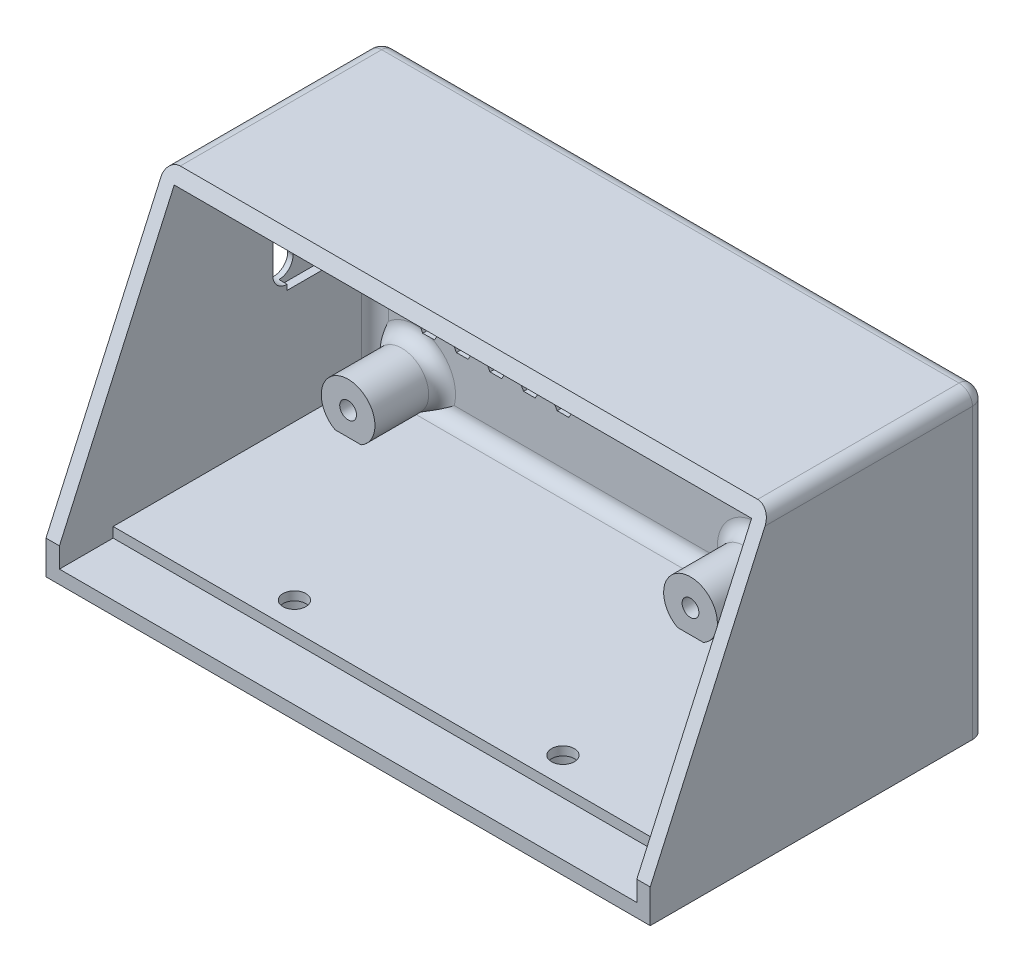
SolidWorks part; units mm, degrees
ref_plane "前视基准面" through (0, 0, 0) normal (0, 0, 1) x (1, 0, 0)
ref_plane "上视基准面" through (0, 0, 0) normal (0, 1, 0) x (1, 0, 0)
ref_plane "右视基准面" through (0, 0, 0) normal (1, 0, 0) x (0, 0, -1)
sketch "草图1" plane through (0, 0, 0) normal (0, 0, 1) x (1, 0, 0)
  line L1 (0, 0) -> (90, 0)
  line L2 (0, 0) -> (0, 45)
  line L3 (0, 45) -> (90, 45)
  line L4 (90, 0) -> (90, 45)
  dimension "D1" = 90
  dimension "D2" = 45
extrude "凸台-拉伸1" add sketch "草图1" along normal blind 50
sketch "草图2" plane through (90, 0, 0) normal (1, 0, 0) x (0, 0, -1)
  line L0 (-32, 45) -> (-50, 5)
  line L1 (-50, 45) -> (0, 45) construction
  line L2 (-50, 0) -> (-50, 45) construction
  line L3 (-50, 5) -> (-50, 45)
  line L4 (-50, 45) -> (-32, 45)
  dimension "D1" = 18
  dimension "D2" = 40
extrude "切除-拉伸1" cut sketch "草图2" against normal through all
ref_plane "基准面1" through (0, 0, 70) normal (0, 0, 1) x (1, 0, 0)
sketch "草图3" plane through (0, 0, 70) normal (0, 0, 1) x (1, 0, 0)
  line L0 (0, 5) -> (0, 45) construction
  line L1 (2, 2) -> (88, 2)
  line L2 (2, 2) -> (2, 43)
  line L3 (2, 43) -> (88, 43)
  line L4 (88, 2) -> (88, 43)
  line L5 (0, 45) -> (90, 45) construction
  line L6 (0, 0) -> (90, 0) construction
  line L7 (90, 5) -> (90, 45) construction
  dimension "D1" = 2
  dimension "D2" = 2
  dimension "D3" = 2
  dimension "D4" = 2
extrude "切除-拉伸2" cut sketch "草图3" against normal offset from surface (67 mm away) 3 up to face at (45, 22.5, 0)
sketch "草图4" plane through (0, 0, 3) normal (0, 0, 1) x (1, 0, 0)
  line L0 (2, 2) -> (88, 2) construction
  line L1 (2, 5) -> (2, 43) construction
  circle A0 centre (8, 38) radius 4
  circle A1 centre (59, 38) radius 4
  circle A2 centre (8, 7) radius 4
  circle A3 centre (59, 7) radius 4
  dimension "D1" = 8
  dimension "D2" = 8
  dimension "D3" = 8
  dimension "D4" = 8
  dimension "D5" = 51
  dimension "D6" = 31
  dimension "D7" = 5
  dimension "D8" = 6
extrude "凸台-拉伸2" add sketch "草图4" along normal blind 10
sketch "草图5" plane through (0, 0, 13) normal (0, 0, 1) x (1, 0, 0)
  circle A0 centre (8, 38) radius 1.25
  circle A1 centre (59, 38) radius 1.25
  circle A2 centre (8, 7) radius 1.25
  circle A3 centre (59, 7) radius 1.25
  dimension "D1" = 2.5
  dimension "D2" = 2.5
  dimension "D3" = 2.5
  dimension "D4" = 2.5
extrude "切除-拉伸3" cut sketch "草图5" against normal blind 7
ref_plane "基准面2" through (0, 0, 9) normal (0, 0, 1) x (1, 0, 0)
sketch "草图6" plane through (0, 0, 9) normal (0, 0, 1) x (1, 0, 0)
  circle A0 centre (8, 38) radius 2.5
  circle A1 centre (59, 38) radius 2.5
  circle A2 centre (8, 7) radius 2.5
  circle A3 centre (59, 7) radius 2.5
  dimension "D1" = 5
  dimension "D2" = 5
  dimension "D3" = 5
  dimension "D4" = 5
extrude "切除-拉伸4" cut sketch "草图6" against normal blind 3
sketch "草图7" plane through (0, 0, 0) normal (-1, 0, 0) x (0, 0, 1)
  line L0 (16.1, 30.1) -> (16.1, 23.9) construction
  line L1 (18.2, 30.1) -> (18.2, 23.9)
  line L2 (14, 30.1) -> (14, 23.9)
  line L3 (0, 45) -> (0, 0) construction
  line L4 (32, 45) -> (0, 45) construction
  arc A0 (18.2, 30.1) -> (14, 30.1) centre (16.1, 30.1) ccw
  arc A1 (14, 23.9) -> (18.2, 23.9) centre (16.1, 23.9) ccw
  point P2 (16.1, 27)
  dimension "D1" = 6.2
  dimension "D2" = 4.2
  dimension "D3" = 16.1
  dimension "D4" = 18
extrude "切除-拉伸5" cut sketch "草图7" against normal up to surface (2 mm away) up to face at (2, 19, 27.78)
sketch "草图8" plane through (2, 0, 0) normal (1, 0, 0) x (0, 0, -1)
  line L0 (-3, 43) -> (-3, 2) construction
  line L1 (-16.1, 33) -> (-3, 33)
  line L2 (-16.1, 33) -> (-16.1, 21)
  line L3 (-16.1, 21) -> (-3, 21)
  line L4 (-3, 33) -> (-3, 21)
  line L5 (-14, 23.9) -> (-14, 30.1) construction
  arc A0 (-14, 30.1) -> (-18.2, 30.1) centre (-16.1, 30.1) ccw construction
  point P9 (-16.1, 32.2)
  point P12 (-14, 27)
  point P13 (-16.1, 27)
  dimension "D1" = 12
extrude "切除-拉伸6" cut sketch "草图8" against normal blind 1.2
sketch "草图9" plane through (0, 0, 0) normal (0, 0, -1) x (-1, 0, 0)
  line L0 (-90, 45) -> (0, 45) construction
  line L1 (-8.2679, 29) -> (-9.134, 30.5)
  line L2 (-9.134, 30.5) -> (-10.866, 30.5)
  line L3 (-10.866, 30.5) -> (-11.7321, 29)
  line L4 (-11.7321, 29) -> (-10.866, 27.5)
  line L5 (-10.866, 27.5) -> (-9.134, 27.5)
  line L6 (-9.134, 27.5) -> (-8.2679, 29)
  line L9 (-14.134, 30.5) -> (-15.866, 30.5)
  line L10 (-13.2679, 29) -> (-14.134, 30.5)
  line L11 (-14.134, 27.5) -> (-13.2679, 29)
  line L12 (-15.866, 27.5) -> (-14.134, 27.5)
  line L13 (-16.7321, 29) -> (-15.866, 27.5)
  line L14 (-15.866, 30.5) -> (-16.7321, 29)
  line L15 (-19.134, 30.5) -> (-20.866, 30.5)
  line L16 (-18.2679, 29) -> (-19.134, 30.5)
  line L17 (-19.134, 27.5) -> (-18.2679, 29)
  line L18 (-20.866, 27.5) -> (-19.134, 27.5)
  line L19 (-21.7321, 29) -> (-20.866, 27.5)
  line L20 (-20.866, 30.5) -> (-21.7321, 29)
  line L21 (-24.134, 30.5) -> (-25.866, 30.5)
  line L22 (-23.2679, 29) -> (-24.134, 30.5)
  line L23 (-24.134, 27.5) -> (-23.2679, 29)
  line L24 (-25.866, 27.5) -> (-24.134, 27.5)
  line L25 (-26.7321, 29) -> (-25.866, 27.5)
  line L26 (-25.866, 30.5) -> (-26.7321, 29)
  line L27 (-29.134, 30.5) -> (-30.866, 30.5)
  line L28 (-28.2679, 29) -> (-29.134, 30.5)
  line L29 (-29.134, 27.5) -> (-28.2679, 29)
  line L30 (-30.866, 27.5) -> (-29.134, 27.5)
  line L31 (-31.7321, 29) -> (-30.866, 27.5)
  line L32 (-30.866, 30.5) -> (-31.7321, 29)
  line L39 (0, 45) -> (0, 0) construction
  line L40 (-8.2679, 24) -> (-9.134, 25.5)
  line L41 (-9.134, 25.5) -> (-10.866, 25.5)
  line L42 (-10.866, 25.5) -> (-11.7321, 24)
  line L43 (-11.7321, 24) -> (-10.866, 22.5)
  line L44 (-10.866, 22.5) -> (-9.134, 22.5)
  line L45 (-9.134, 22.5) -> (-8.2679, 24)
  line L46 (-14.134, 25.5) -> (-15.866, 25.5)
  line L47 (-13.2679, 24) -> (-14.134, 25.5)
  line L48 (-14.134, 22.5) -> (-13.2679, 24)
  line L49 (-15.866, 22.5) -> (-14.134, 22.5)
  line L50 (-16.7321, 24) -> (-15.866, 22.5)
  line L51 (-15.866, 25.5) -> (-16.7321, 24)
  line L52 (-19.134, 25.5) -> (-20.866, 25.5)
  line L53 (-18.2679, 24) -> (-19.134, 25.5)
  line L54 (-19.134, 22.5) -> (-18.2679, 24)
  line L55 (-20.866, 22.5) -> (-19.134, 22.5)
  line L56 (-21.7321, 24) -> (-20.866, 22.5)
  line L57 (-20.866, 25.5) -> (-21.7321, 24)
  line L58 (-24.134, 25.5) -> (-25.866, 25.5)
  line L59 (-23.2679, 24) -> (-24.134, 25.5)
  line L60 (-24.134, 22.5) -> (-23.2679, 24)
  line L61 (-25.866, 22.5) -> (-24.134, 22.5)
  line L62 (-26.7321, 24) -> (-25.866, 22.5)
  line L63 (-25.866, 25.5) -> (-26.7321, 24)
  line L64 (-29.134, 25.5) -> (-30.866, 25.5)
  line L65 (-28.2679, 24) -> (-29.134, 25.5)
  line L66 (-29.134, 22.5) -> (-28.2679, 24)
  line L67 (-30.866, 22.5) -> (-29.134, 22.5)
  line L68 (-31.7321, 24) -> (-30.866, 22.5)
  line L69 (-30.866, 25.5) -> (-31.7321, 24)
  line L70 (-8.2679, 19) -> (-9.134, 20.5)
  line L71 (-9.134, 20.5) -> (-10.866, 20.5)
  line L72 (-10.866, 20.5) -> (-11.7321, 19)
  line L73 (-11.7321, 19) -> (-10.866, 17.5)
  line L74 (-10.866, 17.5) -> (-9.134, 17.5)
  line L75 (-9.134, 17.5) -> (-8.2679, 19)
  line L76 (-14.134, 20.5) -> (-15.866, 20.5)
  line L77 (-13.2679, 19) -> (-14.134, 20.5)
  line L78 (-14.134, 17.5) -> (-13.2679, 19)
  line L79 (-15.866, 17.5) -> (-14.134, 17.5)
  line L80 (-16.7321, 19) -> (-15.866, 17.5)
  line L81 (-15.866, 20.5) -> (-16.7321, 19)
  line L82 (-19.134, 20.5) -> (-20.866, 20.5)
  line L83 (-18.2679, 19) -> (-19.134, 20.5)
  line L84 (-19.134, 17.5) -> (-18.2679, 19)
  line L85 (-20.866, 17.5) -> (-19.134, 17.5)
  line L86 (-21.7321, 19) -> (-20.866, 17.5)
  line L87 (-20.866, 20.5) -> (-21.7321, 19)
  line L88 (-24.134, 20.5) -> (-25.866, 20.5)
  line L89 (-23.2679, 19) -> (-24.134, 20.5)
  line L90 (-24.134, 17.5) -> (-23.2679, 19)
  line L91 (-25.866, 17.5) -> (-24.134, 17.5)
  line L92 (-26.7321, 19) -> (-25.866, 17.5)
  line L93 (-25.866, 20.5) -> (-26.7321, 19)
  line L94 (-29.134, 20.5) -> (-30.866, 20.5)
  line L95 (-28.2679, 19) -> (-29.134, 20.5)
  line L96 (-29.134, 17.5) -> (-28.2679, 19)
  line L97 (-30.866, 17.5) -> (-29.134, 17.5)
  line L98 (-31.7321, 19) -> (-30.866, 17.5)
  line L99 (-30.866, 20.5) -> (-31.7321, 19)
  line L100 (-8.2679, 14) -> (-9.134, 15.5)
  line L101 (-9.134, 15.5) -> (-10.866, 15.5)
  line L102 (-10.866, 15.5) -> (-11.7321, 14)
  line L103 (-11.7321, 14) -> (-10.866, 12.5)
  line L104 (-10.866, 12.5) -> (-9.134, 12.5)
  line L105 (-9.134, 12.5) -> (-8.2679, 14)
  line L106 (-14.134, 15.5) -> (-15.866, 15.5)
  line L107 (-13.2679, 14) -> (-14.134, 15.5)
  line L108 (-14.134, 12.5) -> (-13.2679, 14)
  line L109 (-15.866, 12.5) -> (-14.134, 12.5)
  line L110 (-16.7321, 14) -> (-15.866, 12.5)
  line L111 (-15.866, 15.5) -> (-16.7321, 14)
  line L112 (-19.134, 15.5) -> (-20.866, 15.5)
  line L113 (-18.2679, 14) -> (-19.134, 15.5)
  line L114 (-19.134, 12.5) -> (-18.2679, 14)
  line L115 (-20.866, 12.5) -> (-19.134, 12.5)
  line L116 (-21.7321, 14) -> (-20.866, 12.5)
  line L117 (-20.866, 15.5) -> (-21.7321, 14)
  line L118 (-24.134, 15.5) -> (-25.866, 15.5)
  line L119 (-23.2679, 14) -> (-24.134, 15.5)
  line L120 (-24.134, 12.5) -> (-23.2679, 14)
  line L121 (-25.866, 12.5) -> (-24.134, 12.5)
  line L122 (-26.7321, 14) -> (-25.866, 12.5)
  line L123 (-25.866, 15.5) -> (-26.7321, 14)
  line L124 (-29.134, 15.5) -> (-30.866, 15.5)
  line L125 (-28.2679, 14) -> (-29.134, 15.5)
  line L126 (-29.134, 12.5) -> (-28.2679, 14)
  line L127 (-30.866, 12.5) -> (-29.134, 12.5)
  line L128 (-31.7321, 14) -> (-30.866, 12.5)
  line L129 (-30.866, 15.5) -> (-31.7321, 14)
  circle A0 centre (-10, 29) radius 1.5 construction
  circle A1 centre (-15, 29) radius 1.5 construction
  circle A2 centre (-20, 29) radius 1.5 construction
  circle A3 centre (-25, 29) radius 1.5 construction
  circle A4 centre (-30, 29) radius 1.5 construction
  circle A5 centre (-10, 24) radius 1.5 construction
  circle A6 centre (-15, 24) radius 1.5 construction
  circle A7 centre (-20, 24) radius 1.5 construction
  circle A8 centre (-25, 24) radius 1.5 construction
  circle A9 centre (-30, 24) radius 1.5 construction
  circle A10 centre (-10, 19) radius 1.5 construction
  circle A11 centre (-15, 19) radius 1.5 construction
  circle A12 centre (-20, 19) radius 1.5 construction
  circle A13 centre (-25, 19) radius 1.5 construction
  circle A14 centre (-30, 19) radius 1.5 construction
  circle A15 centre (-10, 14) radius 1.5 construction
  circle A16 centre (-15, 14) radius 1.5 construction
  circle A17 centre (-20, 14) radius 1.5 construction
  circle A18 centre (-25, 14) radius 1.5 construction
  circle A19 centre (-30, 14) radius 1.5 construction
  dimension "D1" = 3
  dimension "D2" = 16
  dimension "D3" = 10
  dimension "D4" = 5
  dimension "D5" = 4
extrude "切除-拉伸7" cut sketch "草图9" against normal up to surface (3 mm away) up to face at (55, 7, 3)
sketch "草图10" plane through (0, 0, 3) normal (0, 0, 1) x (1, 0, 0)
  line L0 (20.866, 30.5) -> (19.134, 30.5) construction
  line L1 (88, 43) -> (2, 43) construction
  circle A0 centre (20, 36.8) radius 4.5
  circle A1 centre (20, 36.8) radius 3.5
  point P6 (20, 30.5)
  dimension "D1" = 9
  dimension "D2" = 7
  dimension "D3" = 6.2
extrude "凸台-拉伸3" add sketch "草图10" along normal blind 3
sketch "草图11" plane through (0, 0, 3) normal (0, 0, 1) x (1, 0, 0)
  circle A0 centre (20, 36.8) radius 2
  dimension "D1" = 4
extrude "切除-拉伸8" cut sketch "草图11" against normal through all
sketch "草图13" plane through (0, 2, 0) normal (0, 1, 0) x (1, 0, 0)
  line L0 (88, -3) -> (88, -50) construction
  line L1 (2, -3) -> (88, -3)
  line L2 (2, -3) -> (2, -42)
  line L3 (2, -42) -> (88, -42)
  line L4 (88, -3) -> (88, -42)
  line L5 (88, -50) -> (2, -50) construction
  dimension "D1" = 8
extrude "凸台-拉伸5" add sketch "草图13" along normal blind 1.5
sketch "草图12" plane through (0, 0, 0) normal (0, -1, 0) x (1, 0, 0)
  line L0 (45, 50) -> (45, -10.3613) construction
  line L1 (0, 50) -> (90, 50) construction
  circle A0 centre (25, 38) radius 1.7
  circle A1 centre (65, 38) radius 1.7
  dimension "D1" = 3.4
  dimension "D3" = 12
  dimension "D2" = 20
extrude "切除-拉伸9" cut sketch "草图12" against normal up to next
sketch "草图14" plane through (0, 0, 0) normal (0, -1, 0) x (1, 0, 0)
  circle A0 centre (25, 38) radius 3.1
  circle A1 centre (65, 38) radius 3.1
  dimension "D1" = 6.2
  dimension "D2" = 6.2
extrude "切除-拉伸10" cut sketch "草图14" against normal blind 2.2
fillet "圆角2" radius 2 5 edges at (0, 22.5, 0) (90, 22.5, 0) (45, 45, 0) (90, 45, 16) (0, 45, 16)
fillet "圆角3" radius 2 11 edges at (2, 38, 3) (2, 12.25, 3) (33.5, 3.5, 3) (74.4682, 3.5, 3) (88, 23.25, 3) (45, 43, 3) (8, 11, 3) (59, 11, 3) (55, 38, 3) (15.5, 36.8, 3) (4, 38, 3)
